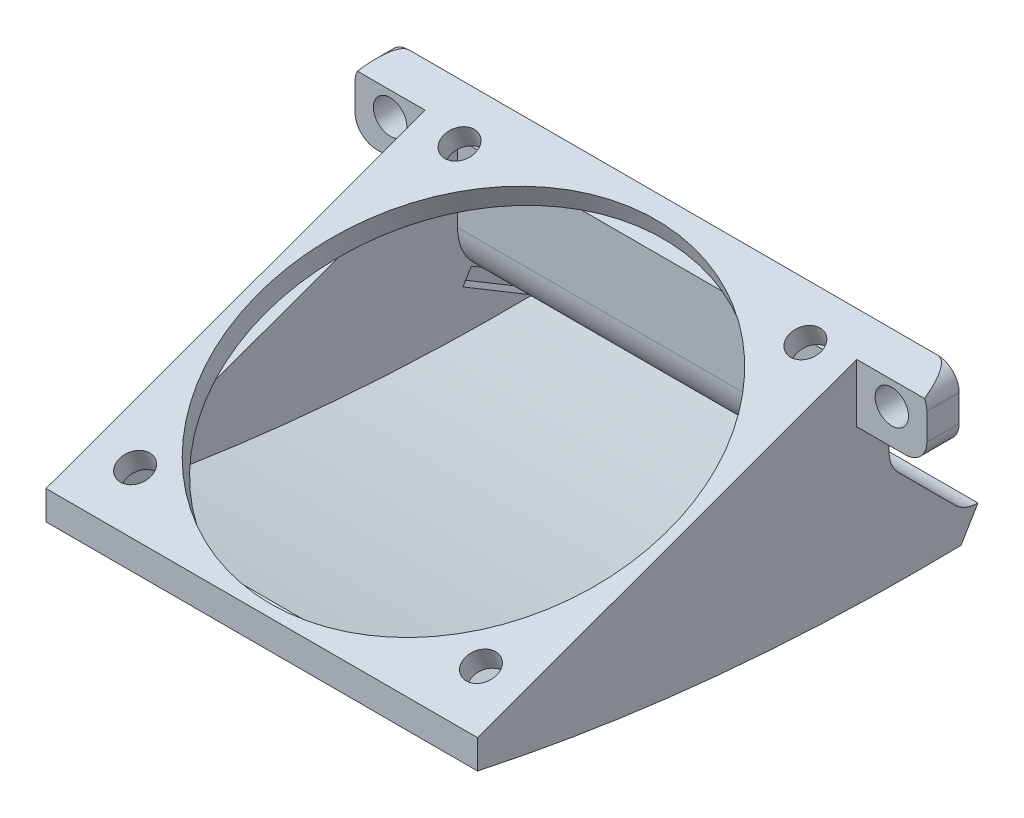
SolidWorks part; units mm, degrees
ref_plane "Ön Düzlem" through (0, 0, 0) normal (0, 0, 1) x (1, 0, 0)
ref_plane "Üst Düzlem" through (0, 0, 0) normal (0, 1, 0) x (1, 0, 0)
ref_plane "Sağ Düzlem" through (0, 0, 0) normal (1, 0, 0) x (0, 0, -1)
sketch "Çizim2" plane through (0, 0, 0) normal (1, 0, 0) x (0, 0, -1)
  line L0 (-8.5206, 2.6552) -> (-8.5206, -7.3448)
  line L1 (-7.5718, -9.534) -> (-2.3993, -14.7088)
  line L2 (-0.278, -15.5875) -> (-1.843, -18.1986)
  line L3 (-8.5206, 2.6552) -> (-46.6659, -11.2286)
  line L4 (-46.6659, -11.2286) -> (-46.6659, -13.9091)
  arc A0 (-8.5206, -7.3448) -> (-7.5718, -9.534) centre (-5.5206, -7.3448) ccw
  arc A1 (-2.3997, -14.7083) -> (-0.278, -15.5875) centre (-0.278, -12.5875) ccw
  spline S0 degree 2 poles (-46.6659, -13.9091) (-24.5169, -18.6739) (-1.843, -18.1986) knots 0 0 0 1 1 1
  point P11 (0, 0)
extrude "Yükseklik-Ekstrüzyon1" add sketch "Çizim2" along normal blind 40 contours L2 A1 L1 A0 L0 region at (0, -10.3399, 21.4432)
shell "İç Boşaltma1" thickness 2 removed face at (20, -16.893, 1.0605)
sketch "Çizim4" plane through (0, -3.9972, -6.6689) normal (0, -0.5141, -0.8577) x (-1, 0, 0)
  line L0 (-39.4, -14.2627) -> (-0.6, -14.2627)
  line L1 (-40, -13.5127) -> (0, -13.5127) construction
  line L5 (-0.6, -14.2627) -> (-0.6, -15.7627)
  line L6 (-39.4, -15.7627) -> (-0.6, -15.7627)
  line L7 (-39.4, -14.2627) -> (-39.4, -15.7627)
  dimension "D1" = 0.75
extrude "Kes-Ekstrüzyon1" cut sketch "Çizim4" against normal blind 10
sketch "Çizim5" plane through (0, 5.083, 1.8501) normal (0, 0.9397, 0.342) x (1, 0, 0)
  line L0 (0, -7.0986) -> (0, -47.692) construction
  line L3 (40, -7.0986) -> (40, -47.692) construction
  circle A0 centre (4, -11.1593) radius 1.45
  circle A1 centre (35.9999, -11.0986) radius 1.45
  circle A2 centre (4, -43.1593) radius 1.45
  circle A3 centre (35.9999, -43.0986) radius 1.45
  circle A4 centre (20, -27.7986) radius 19
  dimension "D5" = 4
  dimension "D6" = 20
  dimension "D1" = 32
  dimension "D2" = 32
  dimension "D3" = 32
  dimension "D4" = 32
extrude "Kes-Ekstrüzyon2" cut sketch "Çizim5" against normal blind 2
sketch "Çizim6" plane through (0, 0, 8.5206) normal (0, 0, -1) x (-1, 0, 0)
  line L0 (-40, 2.6552) -> (-40, -7.3448) construction
  line L1 (-40, 2.6552) -> (-46.5, 2.6552)
  line L2 (-40, 2.6552) -> (-40, -3.8448)
  line L3 (-40, -3.8448) -> (-46.5, -3.8448)
  line L4 (-46.5, 2.6552) -> (-46.5, -3.8448)
  line L5 (0, 2.6552) -> (0, -7.3448) construction
  line L6 (0, 2.6552) -> (6.5, 2.6552)
  line L7 (0, 2.6552) -> (0, -3.8448)
  line L8 (0, -3.8448) -> (6.5, -3.8448)
  line L9 (6.5, 2.6552) -> (6.5, -3.8448)
  line L10 (-40, 2.6552) -> (0, 2.6552) construction
  circle A0 centre (-43.25, -0.5948) radius 1.55
  circle A1 centre (3.25, -0.5948) radius 1.55
  dimension "D3" = 3.25
  dimension "D4" = 3.25
  dimension "D5" = 3.25
  dimension "D2" = 0
  dimension "D6" = 3.25
extrude "Yükseklik-Ekstrüzyon2" add sketch "Çizim6" against normal blind 3
fillet "Radyus1" radius 2 4 edges at (-6.5, -3.8448, 10.0206) (-6.5, 2.6552, 10.0206) (46.5, -3.8448, 10.0206) (46.5, 2.6552, 10.0206)
sketch "Çizim7" plane through (0, 0, 0) normal (-1, 0, 0) x (0, 0, 1)
  line L0 (11.5206, 1.5633) -> (8.5206, 2.6552)
  line L1 (8.5206, 2.6552) -> (11.5206, 2.6552)
  line L2 (11.5206, 2.6552) -> (11.5206, 1.5633)
extrude "Kes-Ekstrüzyon3" cut sketch "Çizim7" against normal blind 55 and the other way blind 10
